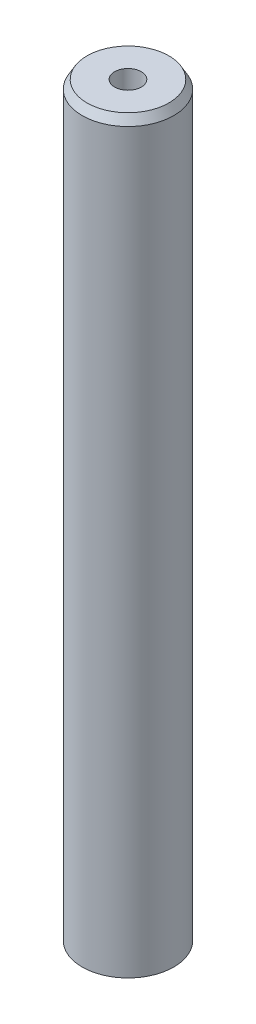
SolidWorks part; units mm, degrees
ref_plane "Front Plane" through (0, 0, 0) normal (0, 0, 1) x (1, 0, 0)
ref_plane "Top Plane" through (0, 0, 0) normal (0, 1, 0) x (1, 0, 0)
ref_plane "Right Plane" through (0, 0, 0) normal (1, 0, 0) x (0, 0, -1)
sketch "Sketch1" plane through (0, 0, 0) normal (0, 1, 0) x (1, 0, 0)
  circle A0 centre (0, 0) radius 12.5
  dimension "SHAFT_OD" = 25
extrude "Boss-Extrude1" add sketch "Sketch1" along normal blind 204.9385
sketch "Sketch2" plane through (0, 0, 0) normal (0, 1, 0) x (1, 0, 0)
  circle A0 centre (0, 0) radius 3.6397
  dimension "BORE_D" = 7.2795
extrude "Cut-Extrude1" cut sketch "Sketch2" along normal through all
chamfer "Chamfer1" distance 2.3205 angle 30 2 edges at (0, 204.9385, 12.5) (0, 0, 12.5) first distance on face at (0, 204.9385, 12.5) first distance on face at (0, 0, 3.6397)
